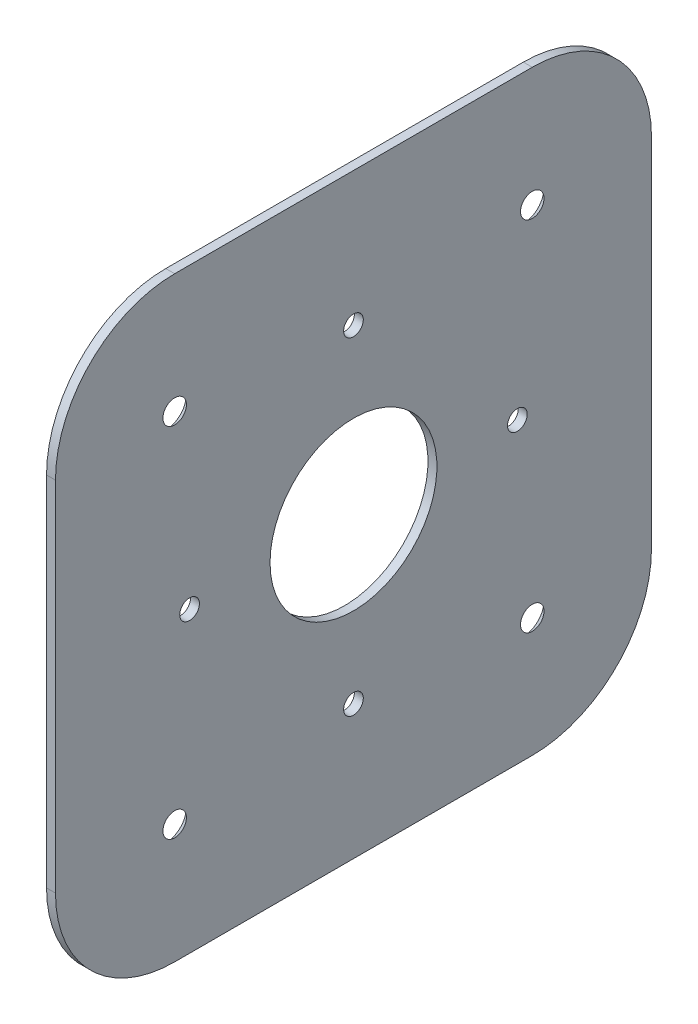
SolidWorks part; units mm, degrees
material "Q235"
ref_plane "前视" through (0, 0, 0) normal (0, 0, 1) x (1, 0, 0)
ref_plane "上视" through (0, 0, 0) normal (0, 1, 0) x (1, 0, 0)
ref_plane "右视" through (0, 0, 0) normal (1, 0, 0) x (0, 0, -1)
sketch "草图1" plane through (0, 0, 0) normal (1, 0, 0) x (0, 0, -1)
  line L1 (-30, -50) -> (30, -50)
  line L2 (-50, -30) -> (-50, 30)
  line L3 (-30, 50) -> (30, 50)
  line L4 (50, -30) -> (50, 30)
  line L5 (-50, -50) -> (50, 50) construction
  line L6 (-50, 50) -> (50, -50) construction
  arc A0 (-30, -50) -> (-50, -30) centre (-30, -30) cw
  arc A1 (30, -50) -> (50, -30) centre (30, -30) ccw
  arc A2 (30, 50) -> (50, 30) centre (30, 30) cw
  arc A3 (-50, 30) -> (-30, 50) centre (-30, 30) cw
  point P0 (0, 0)
  dimension "D2" = 20
  dimension "D1" = 100
sheet metal parameters "钣金1" thickness 1.5 parameters "D1"=1, "厚度"=1.5
base flange "基体-法兰1" sketch "草图1" thickness 1.5 reverse thickness direction no parameters "D1"=1
hole_wizard "M3 六角凹锥坑头螺钉的锥形沉头孔1" positions "草图5" profile "草图4" countersink size "M3" standard "Din" end condition through all
sketch "草图5" plane through (-1.5, 0, 0) normal (-1, 0, 0) x (0, 0, 1)
  line L0 (0, 50) -> (0, 0) construction
  line L1 (-30, 50) -> (30, 50) construction
  line L2 (0, 0) -> (50, 0) construction
  line L3 (50, 30) -> (50, -30) construction
  point P0 (-30, 30)
  point P15 (30, 30)
  point P16 (30, -30)
  point P17 (-30, -30)
  dimension "D1" = 60
  dimension "D2" = 60
sketch "草图4" plane through (-1.5, 30, -30) normal (0, 1, 0) x (0, 0, 1)
  line L0 (0, 0) -> (0, 1.5)
  line L1 (0, 1.5) -> (1.7, 1.5)
  line L2 (1.7, 1.5) -> (1.7, 1.77)
  line L3 (1.7, 1.77) -> (3.47, 0)
  line L5 (3.47, 0) -> (0, 0)
  line L6 (-1.7, 1.77) -> (-3.47, 0) construction
  line L11 (0, -6.35) -> (0, 107.95) construction
  dimension "通孔孔直径" = 3.4
  dimension "通孔孔深度" = 1.5
  dimension "近端锥形沉头孔直径" = 6.94
  dimension "近端锥形沉头孔角度" = 90
hole_wizard "孔1" positions "草图7" profile "草图6" legacy
sketch "草图7" plane through (-1.5, 0, 0) normal (-1, 0, 0) x (0, 0, 1)
  point P0 (0, 0)
sketch "草图6" plane through (-1.5, 0, 0) normal (0, 1, 0) x (0, 0, 1)
  line L0 (0, 0) -> (0, 100)
  line L1 (0, 100) -> (14, 100)
  line L2 (14, 100) -> (14, 0)
  line L3 (14, 0) -> (0, 0)
  line L4 (0, 110) -> (0, -10) construction
  dimension "直径" = 28
  dimension "深度" = 100
hole_wizard "M4 螺纹孔1" positions "草图9" profile "草图8" tap size "M4" standard "Gb" end condition through all
sketch "草图9" plane through (-1.5, 0, 0) normal (-1, 0, 0) x (0, 0, 1)
  circle A0 centre (0, 0) radius 14 construction
  point P0 (0, 27.5)
  dimension "D1" = 27.5
sketch "草图8" plane through (-1.5, 27.5, 0) normal (0, 1, 0) x (0, 0, 1)
  line L0 (0, 0) -> (0, 1.5)
  line L1 (0, 1.5) -> (1.65, 1.5)
  line L2 (1.65, 1.5) -> (1.65, 0)
  line L5 (1.65, 0) -> (0, 0)
  line L11 (0, -6.35) -> (0, 107.95) construction
  dimension "通孔螺纹孔钻头直径" = 3.3
  dimension "通孔螺纹孔钻头深度" = 1.5
cosmetic thread "孔螺蚊线1" parameters "D2"=4
pattern_circular "阵列(圆周)1" count 4 over 360 about axis through (-1.5, 0, 0) along (-1, 0, 0) of "M4 螺纹孔1"
flat pattern "平板型式1" [suppressed]
sketch "折弯-线1" plane through (0, 0, 0) normal (0, 1, 0) x (1, 0, 0)
sketch3d "边界框1" [suppressed]
  line L0 (-80, 80, 0) -> (20, 80, 0) construction
  line L1 (-80, -20, 0) -> (20, -20, 0) construction
  line L2 (-80, 80, 0) -> (-80, -20, 0) construction
  line L3 (20, 80, 0) -> (20, -20, 0) construction
